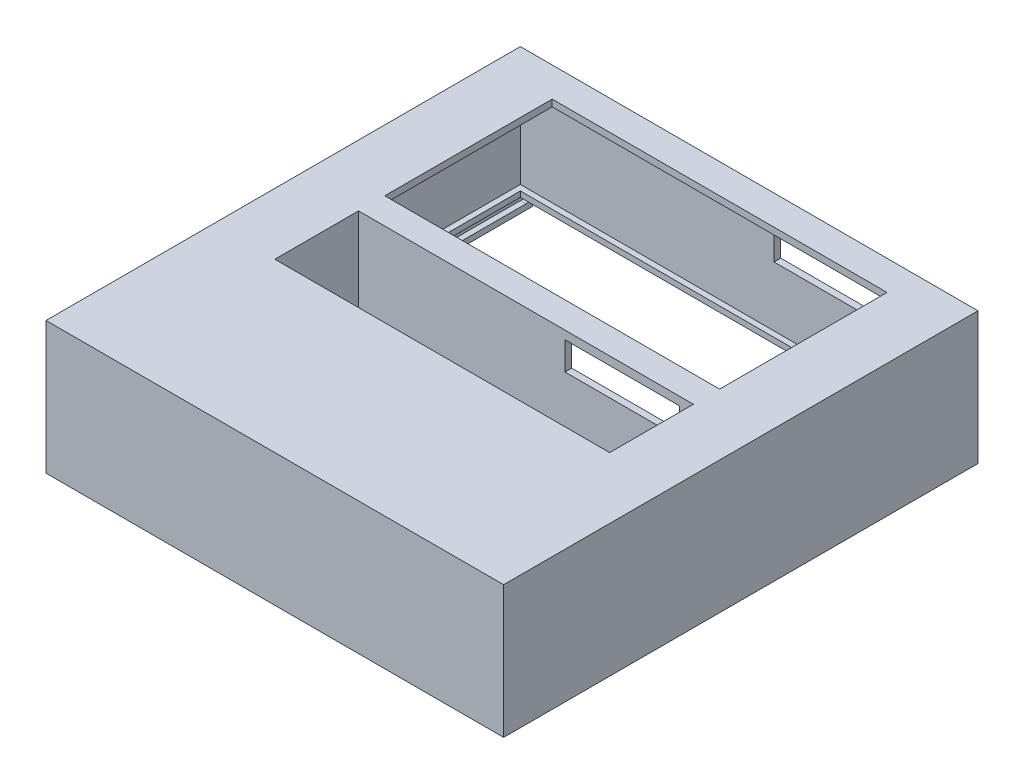
SolidWorks part; units mm, degrees
ref_plane "Front Plane" through (0, 0, 0) normal (0, 0, 1) x (1, 0, 0)
ref_plane "Top Plane" through (0, 0, 0) normal (0, 1, 0) x (1, 0, 0)
ref_plane "Right Plane" through (0, 0, 0) normal (1, 0, 0) x (0, 0, -1)
sketch "Sketch1" plane through (0, 0, 0) normal (0, 1, 0) x (1, 0, 0)
  line L1 (0, 0) -> (82, 0)
  line L2 (0, 0) -> (0, 85)
  line L3 (0, 85) -> (82, 85)
  line L4 (82, 0) -> (82, 85)
  dimension "D1" = 82
  dimension "D2" = 85
extrude "Boss-Extrude1" add sketch "Sketch1" along normal blind 1.2
sketch "Sketch2" plane through (0, 1.2, 0) normal (0, 1, 0) x (1, 0, 0)
  line L0 (0, 83.7) -> (82, 83.7) construction
  line L1 (0, 85) -> (0, 0) construction
  line L2 (82, 0) -> (82, 85) construction
  line L3 (0, 79.7) -> (82, 79.7) construction
  line L4 (0, 49.7) -> (82, 49.7) construction
  line L5 (0, 46.2) -> (82, 46.2) construction
  line L7 (0, 45) -> (82, 45) construction
  line L8 (0, 0) -> (82, 0) construction
  line L10 (11, 79.7) -> (71, 79.7)
  line L11 (11, 79.7) -> (11, 49.7)
  line L12 (11, 49.7) -> (71, 49.7)
  line L13 (71, 79.7) -> (71, 49.7)
  dimension "D1" = 45
  dimension "D2" = 4
  dimension "D3" = 30
  dimension "D4" = 3.5
  dimension "D5" = 1.2
  dimension "D6" = 11
  dimension "D7" = 11
extrude "Cut-Extrude1" cut sketch "Sketch2" against normal blind 2
sketch "Sketch3" plane through (0, 1.2, 0) normal (0, 1, 0) x (1, 0, 0)
  line L0 (11, 85) -> (11, 0) construction
  line L1 (82, 85) -> (0, 85) construction
  line L2 (0, 0) -> (82, 0) construction
  line L3 (71, 85) -> (71, 0) construction
  line L4 (0, 85) -> (0, 0) construction
  line L5 (82, 0) -> (82, 85) construction
  line L7 (11, 45) -> (71, 45)
  line L8 (11, 45) -> (11, 30)
  line L9 (11, 30) -> (71, 30)
  line L10 (71, 45) -> (71, 30)
  dimension "D1" = 11
  dimension "D2" = 11
  dimension "D3" = 30
  dimension "D4" = 15
extrude "Cut-Extrude2" cut sketch "Sketch3" against normal blind 2
sketch "Sketch4" plane through (0, 0, 0) normal (0, -1, 0) x (1, 0, 0)
  line L0 (82, -1.2) -> (0, -1.2) construction
  line L1 (82, 0) -> (82, -85) construction
  line L2 (0, -85) -> (0, 0) construction
  line L3 (1.2, -85) -> (1.2, 0) construction
  line L4 (82, -85) -> (0, -85) construction
  line L5 (0, 0) -> (82, 0) construction
  line L6 (82, -83.8) -> (0, -83.8) construction
  line L7 (80.8, -85) -> (80.8, 0) construction
  line L8 (80.8, -83.8) -> (1.2, -83.8)
  line L9 (1.2, -83.8) -> (1.2, -1.2)
  line L10 (1.2, -1.2) -> (80.8, -1.2)
  line L11 (80.8, -1.2) -> (80.8, -83.8)
  line M13 (0, 0) -> (0, -85)
  line M14 (0, -85) -> (82, -85)
  line M15 (82, -85) -> (82, 0)
  line M16 (82, 0) -> (0, 0)
  dimension "D1" = 1.2
  dimension "D2" = 1.2
  dimension "D3" = 1.2
  dimension "D4" = 1.2
extrude "Boss-Extrude2" add sketch "Sketch4" along normal blind 20 contours L10 L11 L8 L9 M16 M13 M14 M15 region at (41, 0, -1.1811)
sketch "Sketch5" plane through (0, 0, 0) normal (0, -1, 0) x (1, 0, 0)
  line L0 (71, -45) -> (71, -30) construction
  line L1 (72.2, -46.2) -> (9.8, -46.2)
  line L2 (72.2, -46.2) -> (72.2, -28.8)
  line L3 (72.2, -28.8) -> (9.8, -28.8)
  line L4 (9.8, -46.2) -> (9.8, -28.8)
  line L5 (11, -30) -> (11, -45) construction
  line L6 (11, -45) -> (71, -45) construction
  line L7 (71, -30) -> (11, -30) construction
  line M9 (11, -45) -> (11, -30)
  line M10 (11, -30) -> (71, -30)
  line M11 (71, -30) -> (71, -45)
  line M12 (71, -45) -> (11, -45)
  dimension "D1" = 1.2
  dimension "D2" = 1.2
  dimension "D3" = 1.2
  dimension "D4" = 1.2
extrude "Boss-Extrude4" add sketch "Sketch5" along normal blind 20 contours M9 M12 M11 M10 | L2 L3 L4 L1 region at (41, 0, -37.5)
sketch "Sketch10" plane through (0, 0, 0) normal (0, -1, 0) x (1, 0, 0)
  line L0 (9.2, -28.8) -> (9.2, -1.2) construction
  line L1 (72.2, -28.8) -> (9.8, -28.8) construction
  line L2 (1.2, -1.2) -> (80.8, -1.2) construction
  line L3 (1.2, -83.8) -> (1.2, -1.2) construction
  line L5 (9.2, -28.8) -> (10.4, -28.8)
  line L6 (9.2, -28.8) -> (9.2, -25)
  line L7 (9.2, -25) -> (10.4, -25)
  line L8 (10.4, -28.8) -> (10.4, -25)
  dimension "D1" = 8
  dimension "D2" = 3.8
  dimension "D3" = 1.2
extrude "Boss-Extrude5" add sketch "Sketch10" along normal blind 20
sketch "Sketch11" plane through (0, 0, 0) normal (-1, 0, 0) x (0, 0, 1)
  line L0 (-22, -20) -> (-22, 1.2) construction
  line L1 (0, -20) -> (-85, -20) construction
  line L2 (-85, 1.2) -> (0, 1.2) construction
  line L3 (0, 1.2) -> (0, -20) construction
  line L5 (-22, -15) -> (-27, -15)
  line L6 (-22, -15) -> (-22, -3.8)
  line L7 (-22, -3.8) -> (-27, -3.8)
  line L8 (-27, -15) -> (-27, -3.8)
  dimension "D1" = 22
  dimension "D2" = 5
  dimension "D3" = 5
  dimension "D4" = 5
extrude "Cut-Extrude3" cut sketch "Sketch11" against normal blind 1.5
sketch "Sketch12" plane through (0, 0, -85) normal (0, 0, -1) x (-1, 0, 0)
  line L0 (-68.15, -20) -> (-68.15, 1.2) construction
  line L1 (0, -20) -> (-82, -20) construction
  line L2 (-82, 1.2) -> (0, 1.2) construction
  line L3 (-46.65, -20) -> (-46.65, 1.2) construction
  line L4 (-82, 1.2) -> (-82, -20) construction
  line L5 (-68.15, -8.3) -> (-46.65, -8.3)
  line L6 (-68.15, -8.3) -> (-68.15, -0.3)
  line L7 (-68.15, -0.3) -> (-46.65, -0.3)
  line L8 (-46.65, -8.3) -> (-46.65, -0.3)
  dimension "D1" = 13.85
  dimension "D2" = 21.5
  dimension "D3" = 1.5
  dimension "D4" = 8
extrude "Cut-Extrude4" cut sketch "Sketch12" against normal blind 1.5
sketch "Sketch15" plane through (0, 0, -45) normal (0, 0, 1) x (1, 0, 0)
  line L0 (68.5, 1.2) -> (68.5, -20) construction
  line L1 (71, 1.2) -> (11, 1.2) construction
  line L2 (71, -20) -> (11, -20) construction
  line L3 (48, 1.2) -> (48, -20) construction
  line L4 (71, -20) -> (71, 1.2) construction
  line L5 (68.5, -0.3) -> (48, -0.3)
  line L6 (68.5, -0.3) -> (68.5, -5.3)
  line L7 (68.5, -5.3) -> (48, -5.3)
  line L8 (48, -0.3) -> (48, -5.3)
  dimension "D1" = 2.5
  dimension "D2" = 20.5
  dimension "D3" = 1.5
  dimension "D4" = 5
extrude "Cut-Extrude5" cut sketch "Sketch15" against normal blind 1.5 contours L8 L7 L6 L5
sketch "Sketch16" plane through (0, 0, -83.8) normal (0, 0, 1) x (1, 0, 0)
  line L0 (80.8, -20) -> (1.2, -20)
  line L1 (80.8, -20) -> (80.8, -19)
  line L2 (1.2, -20) -> (1.2, -19)
  line L3 (80.8, -19) -> (1.2, -19)
  dimension "D1" = 1
extrude "Boss-Extrude6" add sketch "Sketch16" along normal blind 1 contours L0 L2 L3 L1
sketch "Sketch17" plane through (80.8, 0, 0) normal (-1, 0, 0) x (0, 0, 1)
  line L0 (-82.8, -19) -> (-82.8, -20)
  line L1 (-82.8, -19) -> (-1.2, -19)
  line L2 (-82.8, -20) -> (-1.2, -20)
  line L3 (-1.2, -19) -> (-1.2, -20)
  line L4 (-1.2, -20) -> (-82.8, -20) construction
  point P0 (-2.8938, -20)
extrude "Boss-Extrude7" add sketch "Sketch17" along normal blind 1
sketch "Sketch18" plane through (0, 0, -1.2) normal (0, 0, -1) x (-1, 0, 0)
  line L0 (-79.8, -19) -> (-79.8, -20)
  line L1 (-79.8, -19) -> (-1.2, -19)
  line L2 (-79.8, -20) -> (-1.2, -20)
  line L3 (-1.2, -19) -> (-1.2, -20)
  line L4 (-1.2, -20) -> (-79.8, -20) construction
  point P0 (-3.4182, -20)
extrude "Boss-Extrude8" add sketch "Sketch18" along normal blind 1
sketch "Sketch19" plane through (1.2, 0, 0) normal (1, 0, 0) x (0, 0, -1)
  line L0 (82.8, -19) -> (82.8, -20)
  line L1 (82.8, -19) -> (2.2, -19)
  line L2 (82.8, -20) -> (2.2, -20)
  line L3 (2.2, -19) -> (2.2, -20)
  point P0 (0, 0)
extrude "Boss-Extrude9" add sketch "Sketch19" along normal blind 1
sketch "Sketch20" plane through (0, -20, 0) normal (0, -1, 0) x (1, 0, 0)
  line L0 (0, -85) -> (82, -85) construction
  line L1 (80.8, -1.2) -> (1.2, -1.2)
  line L2 (80.8, -1.2) -> (80.8, -83.8)
  line L3 (80.8, -83.8) -> (1.2, -83.8)
  line L4 (1.2, -1.2) -> (1.2, -83.8)
  line L5 (0, 0) -> (0, -85) construction
  line L6 (82, -85) -> (82, 0) construction
  line L7 (82, 0) -> (0, 0) construction
  line M9 (82, 0) -> (0, 0)
  line M10 (0, 0) -> (0, -85)
  line M11 (0, -85) -> (82, -85)
  line M12 (82, -85) -> (82, 0)
  dimension "D1" = 1.2
  dimension "D2" = 1.2
  dimension "D3" = 1.2
  dimension "D4" = 1.2
extrude "Boss-Extrude10" add sketch "Sketch20" along normal blind 2.5 contours L4 L1 L2 L3 M12 M9 M10 M11 region at (80.8189, -20, -42.5)
sketch "Sketch23" plane through (80.8, 0, 0) normal (-1, 0, 0) x (0, 0, 1)
  line L0 (-1.2, -22.5) -> (-83.8, -22.5)
  line L1 (-1.2, -22.5) -> (-1.2, -21.5033)
  line L2 (-83.8, -22.5) -> (-83.8, -21.5033)
  line L3 (-1.2, -21.5033) -> (-83.8, -21.5033)
  dimension "D1" = 0.9967
extrude "Boss-Extrude11" add sketch "Sketch23" along normal blind 1
sketch "Sketch25" plane through (0, 0, -1.2) normal (0, 0, -1) x (-1, 0, 0)
  line L0 (-79.8, -22.5) -> (-79.8, -21.5033)
  line L1 (-79.8, -22.5) -> (-1.2, -22.5)
  line L2 (-79.8, -21.5033) -> (-1.2, -21.5033)
  line L3 (-1.2, -22.5) -> (-1.2, -21.5033)
  point P0 (0, 0)
extrude "Boss-Extrude13" add sketch "Sketch25" along normal blind 1
sketch "Sketch27" plane through (1.2, 0, 0) normal (1, 0, 0) x (0, 0, -1)
  line L0 (2.2, -22.5) -> (2.2, -21.5033)
  line L1 (2.2, -22.5) -> (83.8, -22.5)
  line L2 (2.2, -21.5033) -> (83.8, -21.5033)
  line L3 (83.8, -22.5) -> (83.8, -21.5033)
  point P0 (0, 0)
extrude "Boss-Extrude14" add sketch "Sketch27" along normal blind 1
sketch "Sketch28" plane through (0, 0, -85) normal (0, 0, -1) x (-1, 0, 0)
  line L0 (-1.2, -22.5) -> (-80.8, -22.5) construction
  line L1 (-1.2, -22.5) -> (-1.2, -20.2) construction
  line L2 (-80.8, -22.5) -> (-80.8, -20.2) construction
  line L3 (-1.2, -20.2) -> (-80.8, -20.2) construction
  line L4 (0, -22.5) -> (-82, -22.5) construction
  line L5 (0, 1.2) -> (0, -22.5) construction
  line L6 (-82, 1.2) -> (-82, -22.5) construction
  line L7 (-79.8, -22.5) -> (-79.8, -21.5)
  line L8 (-80.8, -22.5) -> (-79.8, -22.5) construction
  line L9 (-80.8, -22.5) -> (-80.8, -21.5) construction
  line L10 (-80.8, -21.5) -> (-79.8, -21.5) construction
  line L11 (-79.8, -22.5) -> (-79.8, -21.5) construction
  line L12 (-1.2, -22.5) -> (-2.2, -22.5) construction
  line L13 (-1.2, -22.5) -> (-1.2, -21.5) construction
  line L14 (-1.2, -21.5) -> (-2.2, -21.5) construction
  line L15 (-2.2, -22.5) -> (-2.2, -21.5) construction
  line L16 (-79.8, -21.5) -> (-80.8, -21.5)
  line L17 (-80.8, -21.5) -> (-80.8, -20.2)
  line L18 (-80.8, -20.2) -> (-1.2, -20.2)
  line L19 (-1.2, -20.2) -> (-1.2, -21.5)
  line L20 (-1.2, -21.5) -> (-2.2, -21.5)
  line L21 (-2.2, -21.5) -> (-2.2, -22.5)
  line L22 (-2.2, -22.5) -> (-79.8, -22.5)
  dimension "D1" = 1.2
  dimension "D2" = 1.2
  dimension "D3" = 2.3
  dimension "D4" = 1
  dimension "D5" = 1
  dimension "D6" = 1
  dimension "D7" = 1
extrude "Cut-Extrude7" cut sketch "Sketch28" against normal blind 1.2
